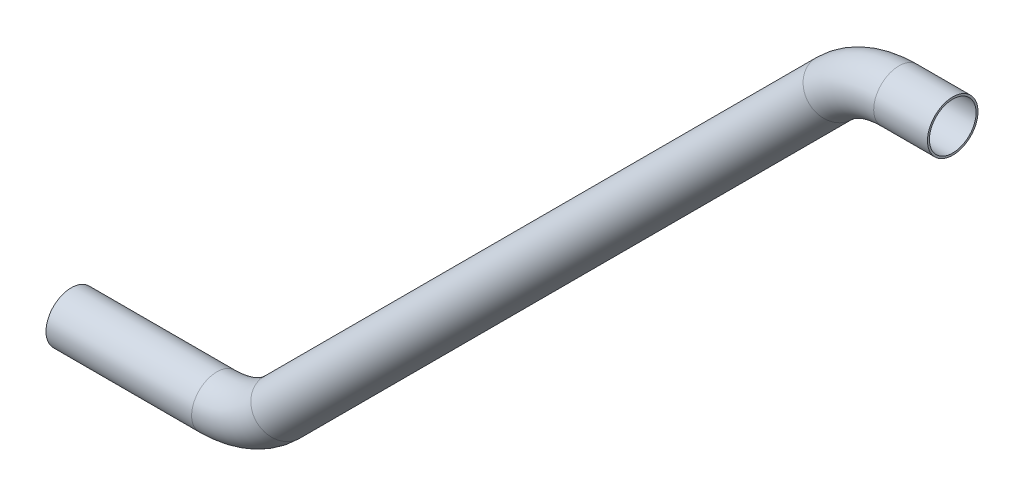
SolidWorks part; units mm, degrees
ref_plane "Front" through (0, 0, 0) normal (0, 0, 1) x (1, 0, 0)
ref_plane "Top" through (0, 0, 0) normal (0, 1, 0) x (1, 0, 0)
ref_plane "Right" through (0, 0, 0) normal (1, 0, 0) x (0, 0, -1)
sketch "Croquis1" plane through (0, 0, 0) normal (0, 0, 1) x (1, 0, 0)
  line L0 (0, 0) -> (237.868, 0)
  line L1 (343.934, 43.934) -> (1246.0155, 946.0155)
  line L2 (1352.0815, 989.9495) -> (1439.9495, 989.9495)
  arc A0 (237.868, 0) -> (343.934, 43.934) centre (237.868, 150) ccw
  arc A1 (1246.0155, 946.0155) -> (1352.0815, 989.9495) centre (1352.0815, 839.9495) cw
  point P7 (300, 0)
  point P10 (1289.9495, 989.9495)
  dimension "D5" = 150
  dimension "D1" = 45
  dimension "D2" = 1400
  dimension "D3" = 300
  dimension "D4" = 150
sweep "Barrer2" add path "Croquis1" circular profile diameter 82.55 parameters "D3"=82.55
shell "Vaciado1" thickness 3.175 removed face at (1439.9495, 989.9495, 41.275)
equation "\"Largo\"= 1500mm"
